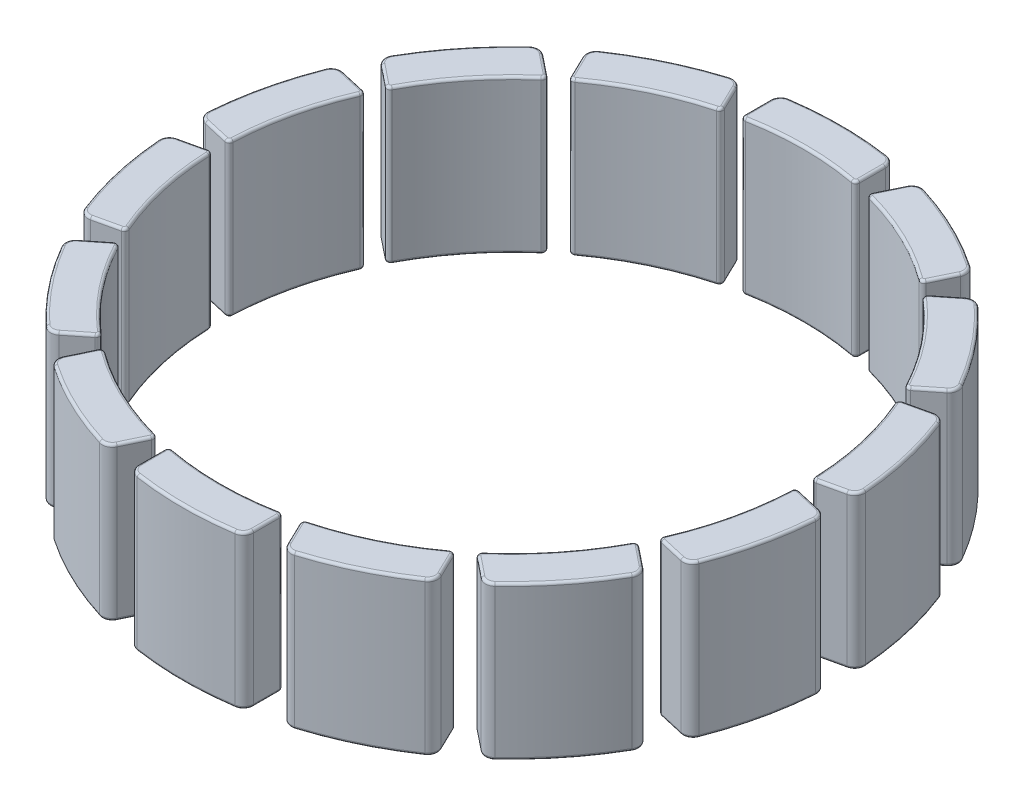
SolidWorks part; units mm, degrees
ref_plane "Alzado" through (0, 0, 0) normal (0, 0, 1) x (1, 0, 0)
ref_plane "Planta" through (0, 0, 0) normal (0, 1, 0) x (1, 0, 0)
ref_plane "Vista lateral" through (0, 0, 0) normal (1, 0, 0) x (0, 0, -1)
sketch "Croquis1" plane through (0, 0, 0) normal (0, 1, 0) x (1, 0, 0)
  line L0 (0, 16.0672) -> (0, -15.7232) construction
  line L1 (-15.3447, 0) -> (15.4135, 0) construction
  line L2 (-2.25, -11.3575) -> (-2.25, -12.3623)
  line L3 (2.25, -12.3623) -> (2.25, -11.3575)
  arc A0 (-1.9092, -12.7579) -> (1.9092, -12.7579) centre (0, 0) ccw
  arc A1 (-2.0727, -11.21) -> (2.0727, -11.21) centre (0, 0) ccw
  arc A2 (-2.25, -12.3623) -> (-1.9092, -12.7579) centre (-1.85, -12.3623) ccw
  arc A3 (2.25, -12.3623) -> (1.9092, -12.7579) centre (1.85, -12.3623) cw
  arc A4 (2.25, -11.3575) -> (2.0727, -11.21) centre (2.1, -11.3575) ccw
  arc A5 (-2.25, -11.3575) -> (-2.0727, -11.21) centre (-2.1, -11.3575) cw
  dimension "D3" = 0.4
  dimension "D4" = 0.15
  dimension "D5" = 12.9
  dimension "D6" = 11.4
  dimension "D1" = 4.5
  dimension "D2" = 4.5
extrude "Saliente-Extruir1" add sketch "Croquis1" along normal blind 6
fillet "Redondeo1" radius 0.1 16 edges at (0, 0, 12.9) (2.1531, 0, 12.6234) (2.25, 0, 11.8599) (2.1959, 0, 11.2422) (0, 0, 11.4) (-2.1959, 0, 11.2422) (-2.25, 0, 11.8599) (-2.1531, 0, 12.6234) (-2.25, 6, 11.8599) (-2.1959, 6, 11.2422) (0, 6, 11.4) (2.1959, 6, 11.2422) (2.25, 6, 11.8599) (2.1531, 6, 12.6234) (0, 6, 12.9) (-2.1531, 6, 12.6234)
pattern_circular "MatrizC3" count 14 over 360 about axis through (0, 5.9, 0) along (0, 1, 0) of bodies 101
